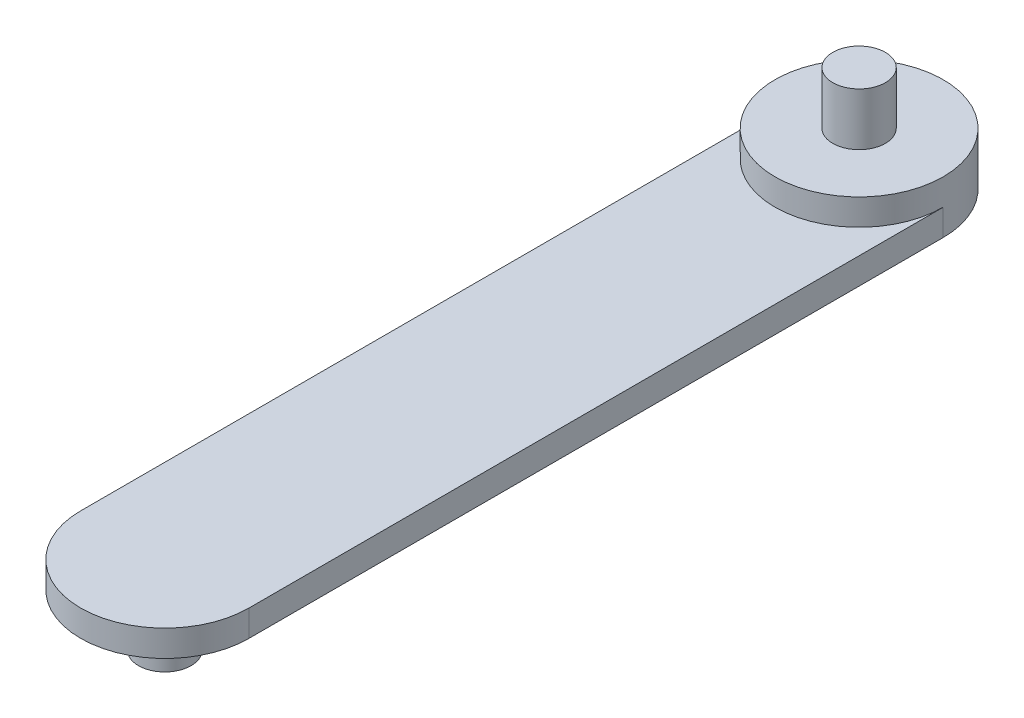
SolidWorks part; units mm, degrees
ref_plane "Front Plane" through (0, 0, 0) normal (0, 0, 1) x (1, 0, 0)
ref_plane "Top Plane" through (0, 0, 0) normal (0, 1, 0) x (1, 0, 0)
ref_plane "Right Plane" through (0, 0, 0) normal (1, 0, 0) x (0, 0, -1)
sketch "Sketch1" plane through (0, 0, 0) normal (0, 1, 0) x (1, 0, 0)
  line L0 (0, 0) -> (0, 33) construction
  line L1 (-4, 0) -> (-4, 33)
  line L2 (4, 0) -> (4, 33)
  arc A0 (-4, 0) -> (4, 0) centre (0, 0) ccw
  arc A1 (4, 33) -> (-4, 33) centre (0, 33) ccw
  circle A4 centre (0, 33) radius 4
  point P3 (0, 16.5)
  dimension "D2" = 4
  dimension "D1" = 33
extrude "Boss-Extrude1" add sketch "Sketch1" along normal blind 2.5 contours A1 A4 region at (0, 0, -33)
extrude "Boss-Extrude5" add sketch "Sketch1<5>" along normal blind 1.25 contours A4 L1 A0 L2 region at (0, 0, -13.3584)
sketch "Sketch1<5>" plane through (0, 0, 0) normal (0, 1, 0) x (1, 0, 0) same geometry as "Sketch1"
sketch "Sketch4" plane through (0, 2.5, 0) normal (0, 1, 0) x (1, 0, 0)
  circle A0 centre (0, 33) radius 1.25
  dimension "D1" = 2.5
extrude "Boss-Extrude6" add sketch "Sketch4" along normal blind 2.5
sketch "Sketch5" plane through (0, 0, 0) normal (0, -1, 0) x (1, 0, 0)
  circle A0 centre (0, 0) radius 1.25
  dimension "D1" = 2.5
extrude "Boss-Extrude7" add sketch "Sketch5" along normal blind 2.5
